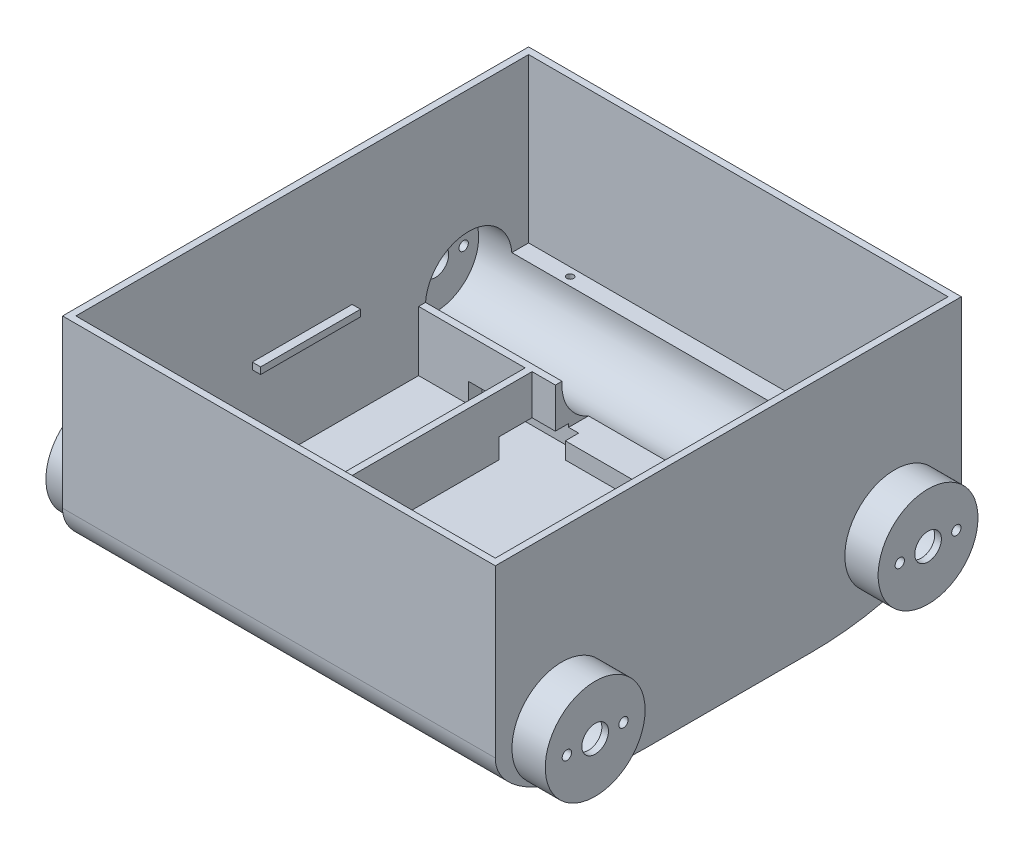
SolidWorks part; units mm, degrees
ref_plane "Спереди" through (0, 0, 0) normal (0, 0, 1) x (1, 0, 0)
ref_plane "Сверху" through (0, 0, 0) normal (0, 1, 0) x (1, 0, 0)
ref_plane "Справа" through (0, 0, 0) normal (1, 0, 0) x (0, 0, -1)
sketch "Эскиз1" plane through (0, 0, 0) normal (0, 1, 0) x (1, 0, 0)
  line L1 (-65, 70) -> (65, 70)
  line L2 (-65, 70) -> (-65, -70)
  line L3 (-65, -70) -> (65, -70)
  line L4 (65, 70) -> (65, -70)
  dimension "D1" = 130
  dimension "D2" = 65
  dimension "D3" = 140
  dimension "D4" = 70
extrude "Бобышка-Вытянуть1" add sketch "Эскиз1" along normal blind 35 and the other way blind 35
sketch "Эскиз2" plane through (65, 0, 0) normal (1, 0, 0) x (0, 0, -1)
  line L0 (-70, -15) -> (70, -15) construction
  line L1 (-70, -35) -> (-70, 35) construction
  line L2 (70, -35) -> (70, 35) construction
  line L3 (-70, -35) -> (70, -35) construction
  line L4 (-25, -35) -> (25, -35)
  line L5 (-70, -40.7424) -> (-70, -15)
  line L7 (-70, -40.7424) -> (70, -40.7424)
  line L8 (70, -40.7424) -> (70, -15)
  ellipse E0 centre (-25, -15) end of major axis (-70, -15) minor radius 20 (-70, -15) -> (-25, -35) ccw
  ellipse E1 centre (25, -15) end of major axis (-20, -15) minor radius 20 (70, -15) -> (25, -35) cw
  point P10 (-25, -15)
  point P11 (25, -15)
  dimension "D1" = 20
  dimension "D2" = 50
  dimension "D3" = 25
  dimension "D4" = 25
  dimension "D5" = 25
extrude "Вырез-Вытянуть1" cut sketch "Эскиз2" against normal blind 130
sketch "Эскиз3" plane through (0, 35, 0) normal (0, 1, 0) x (1, 0, 0)
  line L0 (-65, 70) -> (-65, -70) construction
  line L1 (-63, 68) -> (63, 68)
  line L2 (-63, 68) -> (-63, -68)
  line L3 (-63, -68) -> (63, -68)
  line L4 (63, 68) -> (63, -68)
  line L5 (65, -70) -> (65, 70) construction
  line L6 (-65, -70) -> (65, -70) construction
  line L7 (65, 70) -> (-65, 70) construction
  dimension "D1" = 2
  dimension "D2" = 2
  dimension "D3" = 2
  dimension "D4" = 2
extrude "Вырез-Вытянуть2" cut sketch "Эскиз3" against normal blind 49
sketch "Эскиз4" plane through (0, 0, 0) normal (1, 0, 0) x (0, 0, -1)
  line L0 (-70, -15) -> (70, -15) construction
  circle A0 centre (-50, -15) radius 13
  circle A1 centre (50, -15) radius 13
  ellipse E0 centre (25, -15) end of major axis (70, -15) minor radius 20 (25, -35) -> (70, -15) ccw construction
  point P10 (-50, -15)
  point P11 (50, -15)
  dimension "D3" = 26
  dimension "D4" = 26
  dimension "D1" = 20
  dimension "D2" = 20
extrude "Вырез-Вытянуть3" cut sketch "Эскиз4" against normal blind 63 and the other way blind 63
sketch "Эскиз7" plane through (65, 0, 0) normal (1, 0, 0) x (0, 0, -1)
  line L0 (-70, -15) -> (70, -15) construction
  line L1 (-70, -15) -> (-70, 35) construction
  line L2 (70, -15) -> (70, 35) construction
  line L3 (-70, 35) -> (70, 35) construction
  circle A0 centre (-58.5, -15) radius 1.4
  circle A1 centre (-50, -15) radius 4
  circle A2 centre (-41.5, -15) radius 1.4
  circle A3 centre (41.5, -15) radius 1.4
  circle A4 centre (50, -15) radius 4
  circle A5 centre (58.5, -15) radius 1.4
  point P8 (-50, -15)
  point P9 (50, -15)
  point P10 (-58.5, -15)
  point P11 (-41.5, -15)
  point P12 (58.5, -15)
  point P13 (41.5, -15)
  dimension "D8" = 2.8
  dimension "D9" = 2.8
  dimension "D10" = 2.8
  dimension "D11" = 2.8
  dimension "D12" = 8
  dimension "D13" = 8
  dimension "D1" = 50
  dimension "D2" = 20
  dimension "D3" = 20
  dimension "D4" = 8.5
  dimension "D5" = 8.5
  dimension "D6" = 8.5
  dimension "D7" = 8.5
sketch "Эскиз8" plane through (65, 0, 0) normal (1, 0, 0) x (0, 0, -1)
  line L0 (-70, -15) -> (-70, 35) construction
  circle A0 centre (-50, -15) radius 15
  circle A1 centre (50, -15) radius 15
  dimension "D1" = 20
  dimension "D2" = 30
  dimension "D3" = 20
extrude "Бобышка-Вытянуть3" add sketch "Эскиз8" along normal blind 10
mirror "Зеркальное отражение2" about plane through (0, 0, 0) normal (1, 0, 0) of "Бобышка-Вытянуть3"
extrude "Вырез-Вытянуть6" cut sketch "Эскиз7" along normal blind 32 and the other way blind 160
sketch "Эскиз9" plane through (63, 0, 0) normal (-1, 0, 0) x (0, 0, 1)
  circle A0 centre (-50, -15) radius 13
  circle A1 centre (50, -15) radius 13
  dimension "D1" = 26
  dimension "D2" = 26
extrude "Вырез-Вытянуть7" cut sketch "Эскиз9" against normal blind 10 and the other way blind 136
sketch "Эскиз10" plane through (0, -14, 0) normal (0, 1, 0) x (1, 0, 0)
  line L0 (-63, -37.0385) -> (63, -37.0385) construction
  line L1 (-63, 34.9615) -> (-31, 34.9615)
  line L2 (-63, 34.9615) -> (-63, -35.0385)
  line L3 (-63, -35.0385) -> (-31, -35.0385)
  line L4 (-31, 34.9615) -> (-31, -35.0385)
  line L7 (63, 37.0385) -> (-63, 37.0385) construction
  line L8 (-63, 37.0385) -> (-63, -37.0385) construction
  line L9 (63, -37.0385) -> (63, 37.0385) construction
  line L10 (31, 34.9615) -> (63, 34.9615)
  line L11 (31, 34.9615) -> (31, -35.0385)
  line L12 (31, -35.0385) -> (63, -35.0385)
  line L13 (63, 34.9615) -> (63, -35.0385)
  dimension "D1" = 70
  dimension "D2" = 2
  dimension "D3" = 2.077
  dimension "D4" = 32
  dimension "D5" = 0
  dimension "D6" = 70
  dimension "D7" = 32
  dimension "D8" = 0
  dimension "D9" = 2
extrude "Вырез-Вытянуть8" cut sketch "Эскиз10" against normal blind 18
sketch "Эскиз11" plane through (0, -14, 0) normal (0, 1, 0) x (1, 0, 0)
  line L0 (63, 37.0385) -> (-63, 37.0385) construction
  line L1 (-29, 35.0385) -> (29, 35.0385)
  line L2 (-29, 35.0385) -> (-29, -35.0385)
  line L3 (-29, -35.0385) -> (29, -35.0385)
  line L4 (29, 35.0385) -> (29, -35.0385)
  line L7 (-31, -35.0385) -> (-31, 34.9615) construction
  line L8 (31, 34.9615) -> (31, -35.0385) construction
  line L9 (-63, -35.0385) -> (-31, -35.0385) construction
  dimension "D1" = 2
  dimension "D2" = 0
  dimension "D3" = 2
  dimension "D4" = 2
  dimension "D5" = 58
  dimension "D6" = 70.077
extrude "Вырез-Вытянуть9" cut sketch "Эскиз11" against normal blind 18
sketch "Эскиз13" plane through (0, -14, 0) normal (0, 1, 0) x (1, 0, 0)
  line L3 (-22, 35.0385) -> (22, 35.0385)
  line L4 (-22, 35.0385) -> (-22, 50)
  line L5 (29, 35.0385) -> (-29, 35.0385) construction
  line L6 (-29, -35.0385) -> (29, -35.0385) construction
  line L8 (-22, 50) -> (22, 50)
  line L9 (22, 35.0385) -> (22, 50)
  line L10 (-22, -35.0385) -> (22, -35.0385)
  line L12 (-22, -35.0385) -> (-22, -50)
  line L13 (-22, -50) -> (22, -50)
  line L14 (22, -35.0385) -> (22, -50)
  dimension "D1" = 44
  dimension "D2" = 22
  dimension "D3" = 44
  dimension "D4" = 22
  dimension "D5" = 50
  dimension "D6" = 50
extrude "Вырез-Вытянуть11" cut sketch "Эскиз13" against normal blind 13
sketch "Эскиз14" plane through (0, 0, -35.0385) normal (0, 0, 1) x (1, 0, 0)
  line L0 (-63, -32) -> (-63, -14) construction
  line L1 (-19, -26) -> (-48, -26)
  line L2 (-19, -26) -> (-19, -32)
  line L3 (-19, -32) -> (-48, -32)
  line L4 (-48, -26) -> (-48, -32)
  line L5 (-29, -32) -> (-29, -14) construction
  line L6 (29, -32) -> (-29, -32) construction
  line L7 (-31, -32) -> (-31, -14) construction
  dimension "D1" = 15
  dimension "D2" = 10
  dimension "D3" = 6
  dimension "D4" = 0
  dimension "D5" = 17
extrude "Вырез-Вытянуть12" cut sketch "Эскиз14" against normal blind 4 and the other way blind 10
sketch "Эскиз15" plane through (63, 0, 0) normal (-1, 0, 0) x (0, 0, 1)
  line L0 (35.0385, -14) -> (-34.9615, -14) construction
  line L1 (-15, -3.5) -> (15, -3.5)
  line L2 (-15, -3.5) -> (-15, -5.5)
  line L3 (-15, -5.5) -> (15, -5.5)
  line L4 (15, -3.5) -> (15, -5.5)
  dimension "D1" = 30
  dimension "D2" = 15
  dimension "D3" = 2
  dimension "D4" = 8.5
extrude "Бобышка-Вытянуть4" add sketch "Эскиз15" along normal blind 2.5
mirror "Зеркальное отражение3" about plane through (0, 0, 0) normal (1, 0, 0) of "Бобышка-Вытянуть4"
mirror "Зеркальное отражение4" about plane through (0, 0, 0) normal (1, 0, 0) of "Вырез-Вытянуть12"
sketch "Эскиз16" plane through (0, -14, 0) normal (0, 1, 0) x (1, 0, 0)
  line L0 (-63, 62.9615) -> (63, 62.9615) construction
  line L1 (-63, 68) -> (-63, 62.9615) construction
  circle A0 centre (-48, 65.5015) radius 1
  point P6 (-63, 65.4807)
  dimension "D1" = 2.54
  dimension "D3" = 2
  dimension "D2" = 15
extrude "Вырез-Вытянуть13" cut sketch "Эскиз16" against normal blind 5
mirror "Зеркальное отражение5" about plane through (0, 0, 0) normal (0, 0, 1) of "Вырез-Вытянуть13"
mirror "Зеркальное отражение6" about plane through (0, 0, 0) normal (1, 0, 0) of "Зеркальное отражение5"
